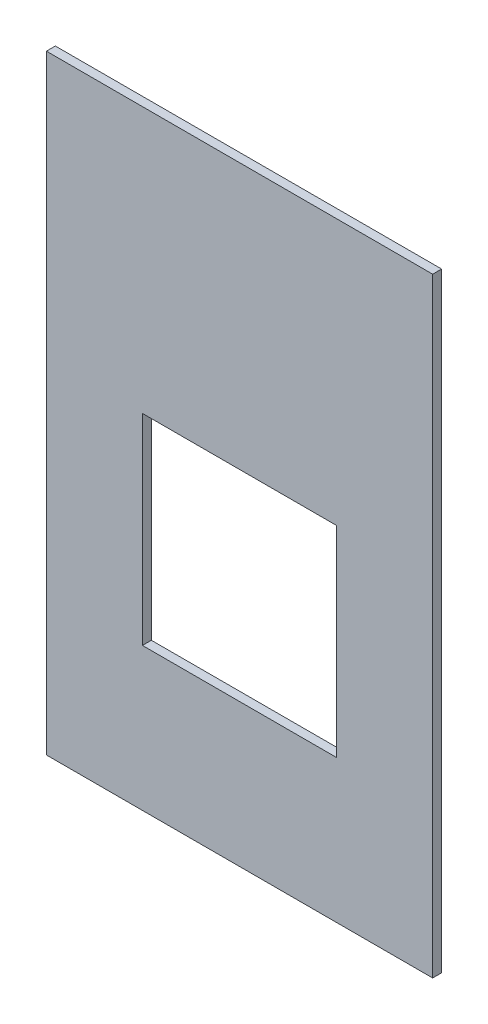
SolidWorks part; units mm, degrees
material "Verre"
ref_plane "Plan de face" through (0, 0, 0) normal (0, 0, 1) x (1, 0, 0)
ref_plane "Plan de dessus" through (0, 0, 0) normal (0, 1, 0) x (1, 0, 0)
ref_plane "Plan de droite" through (0, 0, 0) normal (1, 0, 0) x (0, 0, -1)
sketch "Esquisse1" plane through (0, 0, 0) normal (0, 0, 1) x (1, 0, 0)
  line L1 (0, 0) -> (173, 0)
  line L2 (0, 0) -> (0, 273)
  line L3 (0, 273) -> (173, 273)
  line L4 (173, 0) -> (173, 273)
  line L5 (43, 64) -> (130, 64)
  line L6 (43, 64) -> (43, 154)
  line L7 (43, 154) -> (130, 154)
  line L8 (130, 64) -> (130, 154)
  dimension "D1" = 173
  dimension "D2" = 273
  dimension "D3" = 43
  dimension "D4" = 87
  dimension "D5" = 90
  dimension "D6" = 64
extrude "Boss.-Extru.1" add sketch "Esquisse1" along normal blind 4
